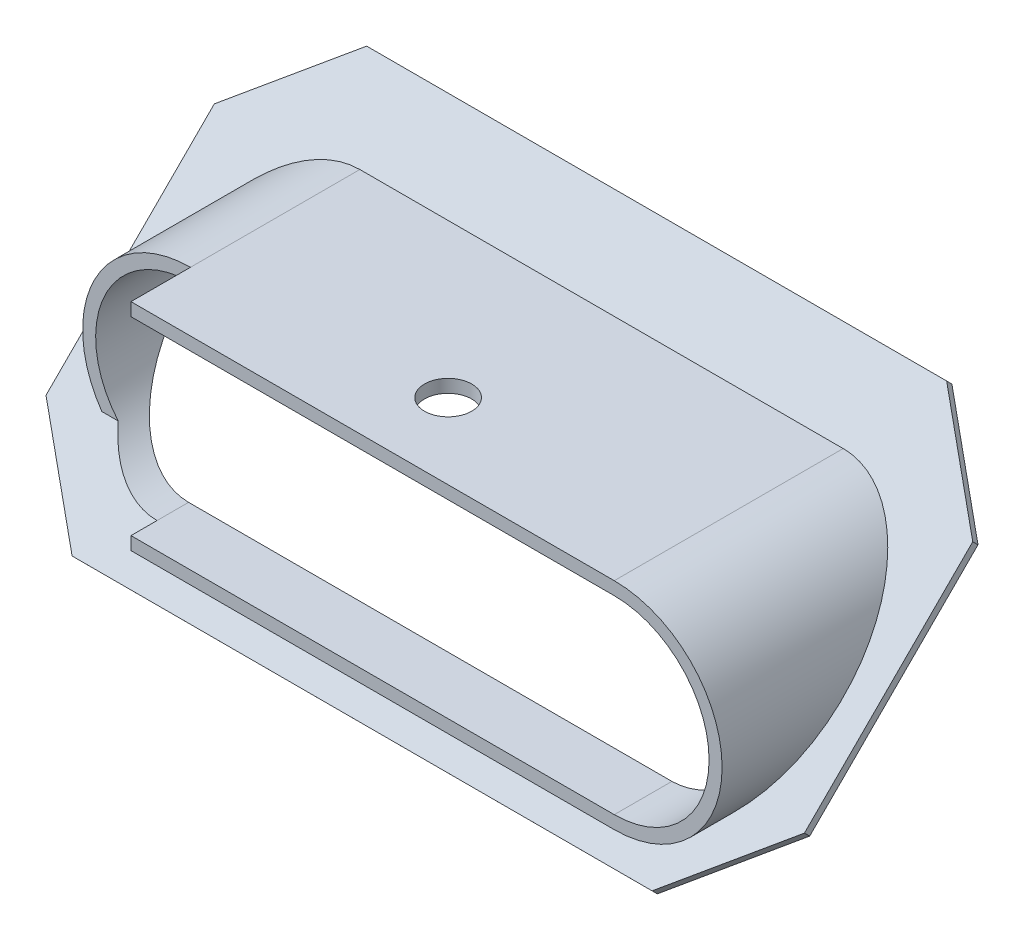
SolidWorks part; units mm, degrees
ref_plane "Front Plane" through (0, 0, 0) normal (0, 0, 1) x (1, 0, 0)
ref_plane "Top Plane" through (0, 0, 0) normal (0, 1, 0) x (1, 0, 0)
ref_plane "Right Plane" through (0, 0, 0) normal (1, 0, 0) x (0, 0, -1)
sketch "Sketch22" plane through (0, 0, 0) normal (0, 0, 1) x (1, 0, 0)
  line L3 (32.5, 0) -> (-32.5, 0) construction
  line L10 (32.5, -14.5) -> (-32.5, -14.5)
  line L11 (32.5, 14.5) -> (-32.5, 14.5)
  arc A2 (32.5, -14.5) -> (32.5, 14.5) centre (32.5, 0) ccw
  arc A3 (-32.5, 14.5) -> (-32.5, -14.5) centre (-32.5, 0) ccw
  point P8 (0, 0)
  point P15 (0, 0)
extrude "Boss-Extrude12" add sketch "Sketch22" along normal blind 80 contours L11 A3 L10 A2 region at (0, 0, 0)
sketch "Sketch34" plane through (0, 0, 0) normal (0, 0, -1) x (-1, 0, 0)
  line L0 (32.5, -14.5) -> (32.5, 14.5) construction
ref_plane "Plane5" through (-32.5, 0, 0) normal (1, 0, 0) x (0, 0, -1)
sketch "Sketch35" plane through (-32.5, 0, 0) normal (1, 0, 0) x (0, 0, -1)
  line L0 (0, 14.5) -> (-29.0269, -14.5)
  line L1 (-80, -14.5) -> (0, -14.5) construction
  line L2 (-29.0269, -14.5) -> (0, -14.5)
  line L3 (0, -14.5) -> (0, 14.5)
extrude "Cut-Extrude10" cut sketch "Sketch35" against normal through all and the other way through all
ref_plane "Plane6" through (0, 7.2567, 7.25) normal (0, -0.7074, -0.7068) x (-1, 0, 0)
sketch "Sketch37" plane through (0, 7.2567, 7.25) normal (0, -0.7074, -0.7068) x (-1, 0, 0)
  line L0 (0, 10.2483) -> (0, -30.7829) construction
  line L1 (-32.5, 10.2483) -> (32.5, 10.2483) construction
  line L2 (32.5, -30.7829) -> (-32.5, -30.7829) construction
  line L4 (51, 17.7327) -> (-51, 17.7327)
  line L5 (51, 17.7327) -> (51, -38.2673)
  line L6 (51, -38.2673) -> (-51, -38.2673)
  line L7 (-51, 17.7327) -> (-51, -38.2673)
  line L8 (51, 17.7327) -> (-51, -38.2673) construction
  line L9 (51, -38.2673) -> (-51, 17.7327) construction
  point P6 (0, -10.2673)
extrude "Boss-Extrude16" add sketch "Sketch37" against normal blind 3
sketch "Sketch38" plane through (0, 0, 80) normal (0, 0, 1) x (1, 0, 0)
  line L0 (32.5, -14.5) -> (32.5, 14.5)
  line L1 (-32.5, 0) -> (32.5, 0) construction
  line L2 (-32.5, 12.75) -> (32.5, 12.75)
  line L3 (-32.5, -12.75) -> (32.5, -12.75)
  arc A0 (-32.5, 12.75) -> (-32.5, -12.75) centre (-32.5, 0) ccw
  arc A1 (32.5, -12.75) -> (32.5, 12.75) centre (32.5, 0) ccw
  point P6 (0, 0)
extrude "Cut-Extrude11" cut sketch "Sketch38" against normal through all contours L3 A1 L2 A0
sketch "Sketch40" plane through (0, -12.75, 0) normal (0, 1, 0) x (1, 0, 0)
  line L0 (32.5, -27.2752) -> (32.5, -35.025) construction
  line L1 (32.5, -27.2752) -> (32.5, -80) construction
  line L2 (-32.5, -27.2752) -> (-32.5, -35.025) construction
  line L3 (-32.5, -27.2752) -> (-32.5, -80) construction
  line L4 (-32.5, -35.025) -> (32.5, -35.025) construction
  line L6 (69.7281, -35.025) -> (-57.7587, -35.025)
  line L7 (-57.7587, -35.025) -> (-57.7587, -89.8582)
  line L8 (-57.7587, -89.8582) -> (69.7281, -89.8582)
  line L9 (69.7281, -89.8582) -> (69.7281, -35.025)
extrude "Cut-Extrude12" cut sketch "Sketch40" along normal through all and the other way up to surface (1.75 mm away) other way up to face at (0, -14.5, 56.6357)
sketch "Sketch42" plane through (-51, 0, 0) normal (-1, 0, 0) x (0, 0, 1)
  line L0 (35.025, 14.5) -> (27.025, 14.5)
  line L1 (35.025, 14.5) -> (4.2446, 14.5) construction
  line L2 (27.025, 14.5) -> (27.025, -8.2593)
  line L3 (36.4419, -17.6675) -> (-3.1744, 21.9121) construction
  line L4 (27.025, -8.2593) -> (33.2715, -14.5)
  line L5 (33.2715, -14.5) -> (35.025, -14.5)
  line L6 (35.025, -14.5) -> (35.025, 14.5)
extrude "Cut-Extrude14" cut sketch "Sketch42" against normal up to vertex (18.5 mm away) up to point (-32.5, -12.75, 35.025)
hole_wizard "1/4 (0.25) Diameter Hole1" positions "Sketch46" profile "Sketch48" hole size "1/4" standard "ANSI Inch"
sketch "Sketch46" plane through (0, 14.5, 0) normal (0, 1, 0) x (1, 0, 0)
  point P2 (0, -24.875)
sketch "Sketch48" plane through (0, 14.5, 24.875) normal (1, 0, 0) x (0, 0, 1)
  line L0 (0, 0) -> (0, 6.9077)
  line L1 (0, 6.9077) -> (3.175, 5)
  line L2 (3.175, 5) -> (3.175, 0)
  line L5 (3.175, 0) -> (0, 0)
  line L10 (0, 6.9077) -> (-3.175, 5) construction
  line L11 (0, -6.35) -> (0, 107.95) construction
  dimension "Hole Dia." = 6.35
  dimension "Hole Depth" = 5
  dimension "Drill Angle" = 118
chamfer "Chamfer2" distance 12 angle 45 4 edges at (-51, 20.851, -4.2346) (51, 20.851, -4.2346) (51, -18.7287, 35.3818) (-51, -18.7287, 35.3818)
chamfer "Chamfer3" distance 2 angle 45 8 edges at (45, -15.5491, 30.077) (51, 0, 14.5134) (45, 15.5491, -1.0501) (0, 19.7898, -5.2947) (0, -19.7898, 34.3216) (-45, -15.5491, 30.077) (-51, 0, 14.5134) (-45, 15.5491, -1.0501)
